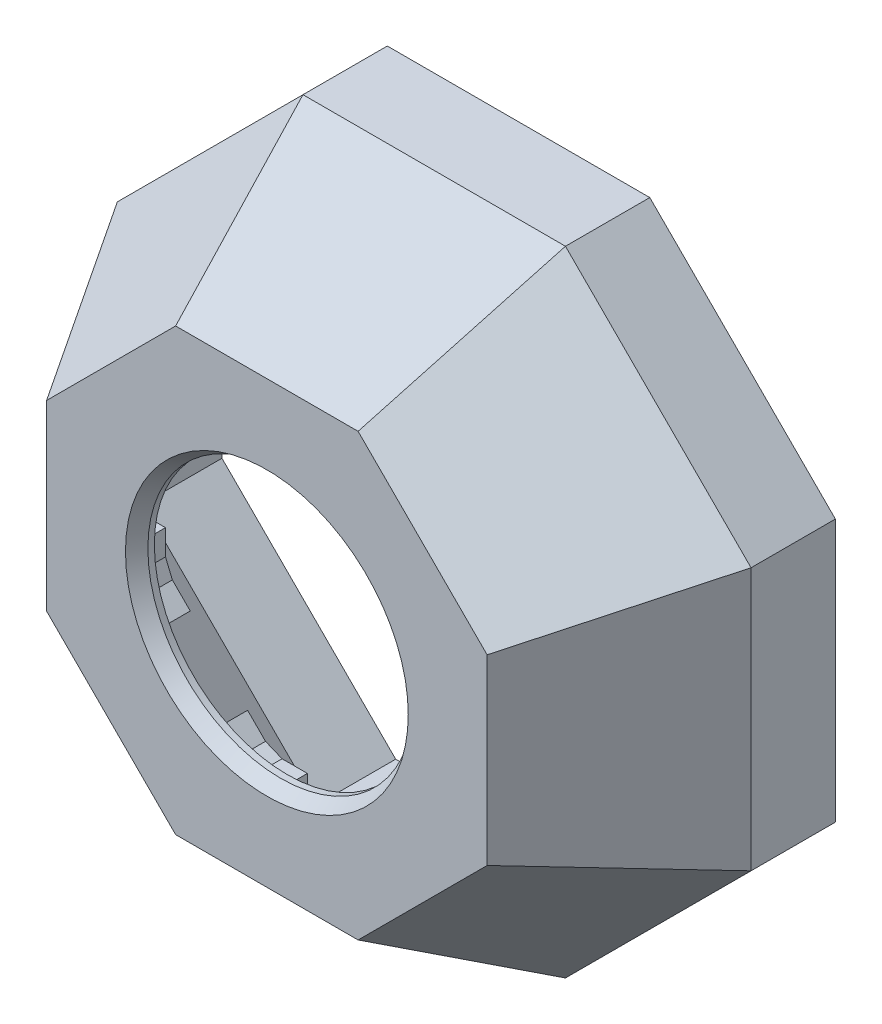
SolidWorks part; units mm, degrees
note: '?' marks a value the reader was unsure of. The reader was unsure of these and kept them because the rebuilt part matched: shared geometry of "Sketch5<2>".
ref_plane "Front Plane" through (0, 0, 0) normal (0, 0, 1) x (1, 0, 0)
ref_plane "Top Plane" through (0, 0, 0) normal (0, 1, 0) x (1, 0, 0)
ref_plane "Right Plane" through (0, 0, 0) normal (1, 0, 0) x (0, 0, -1)
sketch "Sketch1" plane through (0, 0, 0) normal (0, 0, 1) x (1, 0, 0)
  line L1 (21.73, -9.0009) -> (21.73, 9.0009)
  line L2 (21.73, 9.0009) -> (9.0009, 21.73)
  line L3 (9.0009, 21.73) -> (-9.0009, 21.73)
  line L4 (-9.0009, 21.73) -> (-21.73, 9.0009)
  line L5 (-21.73, 9.0009) -> (-21.73, -9.0009)
  line L6 (-21.73, -9.0009) -> (-9.0009, -21.73)
  line L7 (-9.0009, -21.73) -> (9.0009, -21.73)
  line L8 (9.0009, -21.73) -> (21.73, -9.0009)
  circle A0 centre (0, 0) radius 21.73 construction
  point P1 (0, 21.73)
  dimension "D1" = 43.46
ref_plane "Plane1" through (0, 0, -16.51) normal (0, 0, 1) x (1, 0, 0)
sketch "Sketch2" plane through (0, 0, -16.51) normal (0, 0, 1) x (1, 0, 0)
  line L1 (-31.26, -12.9483) -> (-12.9483, -31.26)
  line L2 (-12.9483, -31.26) -> (12.9483, -31.26)
  line L3 (12.9483, -31.26) -> (31.26, -12.9483)
  line L4 (31.26, -12.9483) -> (31.26, 12.9483)
  line L5 (31.26, 12.9483) -> (12.9483, 31.26)
  line L6 (12.9483, 31.26) -> (-12.9483, 31.26)
  line L7 (-12.9483, 31.26) -> (-31.26, 12.9483)
  line L8 (-31.26, 12.9483) -> (-31.26, -12.9483)
  circle A0 centre (0, 0) radius 31.26 construction
  dimension "D1" = 62.52
loft "Loft1" add profiles "Sketch1", "Sketch2"
sketch "Sketch3" plane through (0, 0, -16.51) normal (0, 0, -1) x (-1, 0, 0)
  line L8 (31.26, -12.9483) -> (31.26, 12.9483)
  line L9 (31.26, 12.9483) -> (12.9483, 31.26)
  line L10 (12.9483, 31.26) -> (-12.9483, 31.26)
  line L11 (-12.9483, 31.26) -> (-31.26, 12.9483)
  line L12 (-31.26, 12.9483) -> (-31.26, -12.9483)
  line L13 (-31.26, -12.9483) -> (-12.9483, -31.26)
  line L14 (-12.9483, -31.26) -> (12.9483, -31.26)
  line L15 (12.9483, -31.26) -> (31.26, -12.9483)
  line L16 (31.26, -12.9483) -> (31.26, 12.9483)
  line L17 (31.26, 12.9483) -> (12.9483, 31.26)
  line L18 (12.9483, 31.26) -> (-12.9483, 31.26)
  line L19 (-12.9483, 31.26) -> (-31.26, 12.9483)
  line L20 (-31.26, 12.9483) -> (-31.26, -12.9483)
  line L21 (-31.26, -12.9483) -> (-12.9483, -31.26)
  line L22 (-12.9483, -31.26) -> (12.9483, -31.26)
  line L23 (12.9483, -31.26) -> (31.26, -12.9483)
  dimension "D1" = 0
extrude "Boss-Extrude1" add sketch "Sketch3" along normal blind 8.32
shell "Shell1" thickness 2
sketch "Sketch4" plane through (0, 0, -2) normal (0, 0, -1) x (-1, 0, 0)
  circle A0 centre (0, 0) radius 12.7
  dimension "D1" = 25.4
extrude "Cut-Extrude1" cut sketch "Sketch4" against normal up to next
sketch "Sketch5" plane through (0, 0, 0) normal (1, 0, 0) x (0, 0, -1)
  line L0 (17.0458, 29.26) -> (2, 20.5752)
  line L1 (17.0458, 29.26) -> (2, 20.5752) construction
  line L2 (2, 20.5752) -> (2, 12.7)
  line L3 (2, -12.7) -> (2, -20.5752)
  line L4 (2, -12.7) -> (2, -20.5752) construction
  line L5 (2, 20.5752) -> (2, 12.7) construction
  line L6 (8, 21) -> (8, 24.0385)
  line L7 (8, 24.0385) -> (2, 20.5752)
  line L8 (2, 20.5752) -> (2, 18)
  line L9 (2, 18) -> (8, 18)
  line L10 (8, 18) -> (8, 19)
  arc A0 (8, 21) -> (8, 19) centre (8, 20) ccw
  dimension "D1" = 2
  dimension "D2" = 8
  dimension "D3" = 20
  dimension "D4" = 1
extrude "Boss-Extrude3" add sketch "Sketch5" along normal blind 2.5 from offset 4
extrude "Boss-Extrude4" add sketch "Sketch5<2>" against normal blind 2.5 from offset 4 offset against normal yes
sketch "Sketch5<2>" plane through (0, 0, 0) normal (1, 0, 0) x (0, 0, -1) same geometry as "Sketch5"
ref_plane "Plane3" through (0, 0, 0) normal (0.9239, 0.3827, 0) x (-0.2028, 0.4895, -0.8481)
ref_plane "Plane4" through (0, 0, 0) normal (0.9239, -0.3827, 0) x (0.2028, 0.4895, -0.8481)
ref_axis "Axis1" through (0, 0, -26.0715) along (0, 0, 1)?
pattern_circular "CirPattern1" count 8 over 360 about axis through (0, 0, 0) along (0, 0, 1) of "Boss-Extrude3", "Boss-Extrude4"
chamfer "Chamfer1" distance 2 angle 32 1 edges at (12.7, 0, 0)
sketch "Sketch6" plane through (0, 0, -8) normal (0, 0, -1) x (-1, 0, 0)
  line L0 (17.3241, -8.1317) -> (21.594, -12.4016)
  line L1 (21.594, -12.4016) -> (24.0385, -6.5)
  line L2 (24.0385, -6.5) -> (18, -6.5)
  line L3 (18, -6.5) -> (17.3241, -8.1317)
  line L4 (18, 6.5) -> (17.3241, 8.1317)
  line L5 (17.3241, 8.1317) -> (21.594, 12.4016)
  line L6 (21.594, 12.4016) -> (24.0385, 6.5)
  line L7 (24.0385, 6.5) -> (18, 6.5)
  line L8 (6.5, 18) -> (8.1317, 17.3241)
  line L9 (8.1317, 17.3241) -> (12.4016, 21.594)
  line L10 (12.4016, 21.594) -> (6.5, 24.0385)
  line L11 (6.5, 24.0385) -> (6.5, 18)
  line L12 (-8.1317, 17.3241) -> (-6.5, 18)
  line L13 (-6.5, 18) -> (-6.5, 24.0385)
  line L14 (-6.5, 24.0385) -> (-12.4016, 21.594)
  line L15 (-12.4016, 21.594) -> (-8.1317, 17.3241)
  line L16 (-18, 6.5) -> (-17.3241, 8.1317)
  line L17 (-17.3241, 8.1317) -> (-21.594, 12.4016)
  line L18 (-21.594, 12.4016) -> (-24.0385, 6.5)
  line L19 (-24.0385, 6.5) -> (-18, 6.5)
  line L20 (-17.3241, -8.1317) -> (-18, -6.5)
  line L21 (-18, -6.5) -> (-24.0385, -6.5)
  line L22 (-24.0385, -6.5) -> (-21.594, -12.4016)
  line L23 (-21.594, -12.4016) -> (-17.3241, -8.1317)
  line L24 (-12.4016, -21.594) -> (-6.5, -24.0385)
  line L25 (-6.5, -24.0385) -> (-6.5, -18)
  line L26 (-6.5, -18) -> (-8.1317, -17.3241)
  line L27 (-8.1317, -17.3241) -> (-12.4016, -21.594)
  line L28 (6.5, -24.0385) -> (12.4016, -21.594)
  line L29 (12.4016, -21.594) -> (8.1317, -17.3241)
  line L30 (8.1317, -17.3241) -> (6.5, -18)
  line L31 (6.5, -18) -> (6.5, -24.0385)
extrude "Boss-Extrude5" add sketch "Sketch6" against normal up to body separate body
chamfer "Chamfer2" distance 2 angle 32 24 edges at (18, -5.25, -2) (17.6621, -7.3159, -2) (16.4402, -9.0156, -2) (16.4402, 9.0156, -2) (18, 5.25, -2) (17.6621, 7.3159, -2) (5.25, 18, -2) (7.3159, 17.6621, -2) (9.0156, 16.4402, -2) (-5.25, 18, -2) (-7.3159, 17.6621, -2) (-9.0156, 16.4402, -2) (-16.4402, 9.0156, -2) (-17.6621, 7.3159, -2) (-18, 5.25, -2) (-18, -5.25, -2) (-17.6621, -7.3159, -2) (-16.4402, -9.0156, -2) (-9.0156, -16.4402, -2) (-7.3159, -17.6621, -2) (-5.25, -18, -2) (5.25, -18, -2) (7.3159, -17.6621, -2) (9.0156, -16.4402, -2)
chamfer "Chamfer3" distance 1.5 angle 45 16 edges at (10.1029, -15.7597, -2) (4, -18.2876, -2) (-4, -18.2876, -2) (-10.1029, -15.7597, -2) (-15.7597, -10.1029, -2) (-18.2876, -4, -2) (-15.7597, 10.1029, -2) (-18.2876, 4, -2) (-10.1029, 15.7597, -2) (-4, 18.2876, -2) (4, 18.6627, -2) (10.3681, 16.025, -2) (15.7597, 10.1029, -2) (18.2876, 4, -2) (18.6627, -4, -2) (16.025, -10.3681, -2)
sketch "Sketch7" plane through (0, 0, -2) normal (0, 0, -1) x (-1, 0, 0)
  circle A2 centre (0, 0) radius 13.1
  circle A3 centre (0, 0) radius 13.1
  dimension "D1" = 0.4
extrude "Cut-Extrude2" cut sketch "Sketch7" against normal blind 10
